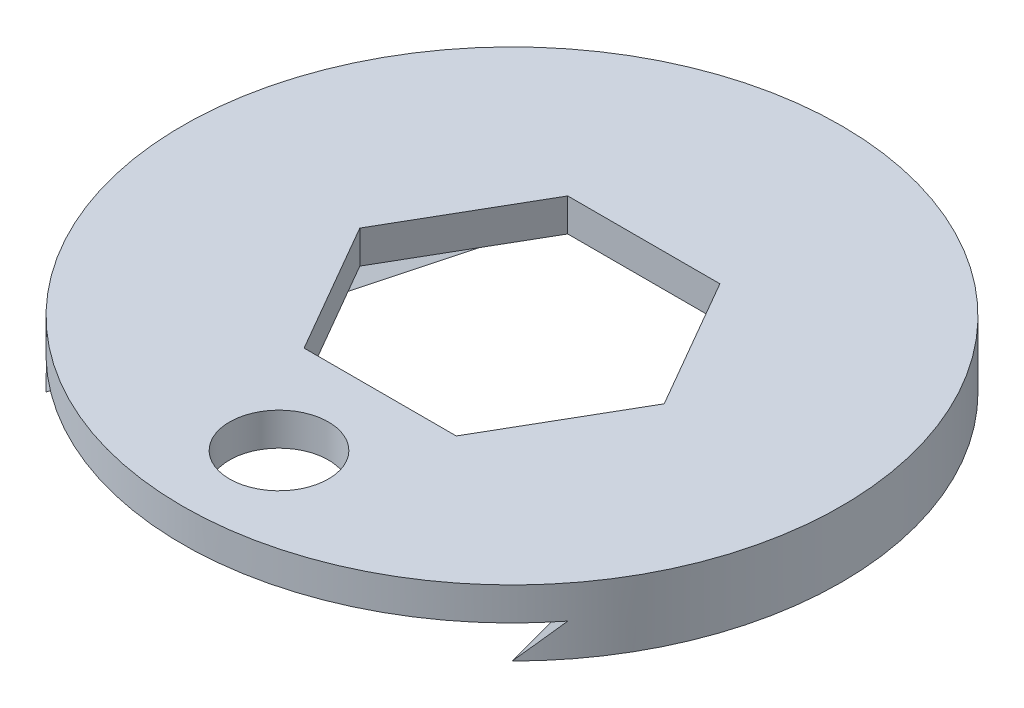
SolidWorks part; units mm, degrees
ref_plane "Front Plane" through (0, 0, 0) normal (0, 0, 1) x (1, 0, 0)
ref_plane "Top Plane" through (0, 0, 0) normal (0, 1, 0) x (1, 0, 0)
ref_plane "Right Plane" through (0, 0, 0) normal (1, 0, 0) x (0, 0, -1)
sketch "Sketch1" plane through (0, 0, 0) normal (0, 1, 0) x (1, 0, 0)
  line L0 (-35.3553, -35.3553) -> (-12.941, 48.2963)
  line L1 (-35.3553, -35.3553) -> (35.3553, -35.3553) construction
  line L2 (-35.3553, -35.3553) -> (-35.3553, 35.3553) construction
  line L3 (-35.3553, 35.3553) -> (35.3553, 35.3553) construction
  line L4 (35.3553, -35.3553) -> (35.3553, 35.3553) construction
  line L5 (-35.3553, -35.3553) -> (35.3553, 35.3553) construction
  line L6 (-35.3553, 35.3553) -> (35.3553, -35.3553) construction
  line L7 (0, 96.5926) -> (0, -94.4212) construction
  line L8 (35.3553, -35.3553) -> (12.941, 48.2963)
  circle A0 centre (0, 0) radius 50
  circle A1 centre (0, -35.3553) radius 7.5
  dimension "D1" = 100
  dimension "D3" = 15
  dimension "D2" = 15
extrude "Boss-Extrude1" add sketch "Sketch1" along normal blind 5 contours A0
extrude "Boss-Extrude2" add sketch "Sketch1<5>" against normal blind 5 contours L8 A0 | L0 A0 region at (-34.0499, 0, -9.1236) region at (34.0499, 0, -9.1236)
sketch "Sketch1<5>" plane through (0, 0, 0) normal (0, 1, 0) x (1, 0, 0) same geometry as "Sketch1"
draft "Draft1" type of draft neutral plane draft angle 45 faces to draft 2 face at (24.1481, -2.5, -6.4705) face at (-24.1481, -2.5, -6.4705) neutral plane through (0, -5, 0) neutral plane normal (0, -1, 0) reverse direction yes parameters "D1"=45
extrude "Cut-Extrude2" cut sketch "Sketch1<8>" against normal through all both and the other way through all contours A1 region at (0, 0, 35.3553)
sketch "Sketch1<8>" plane through (0, 0, 0) normal (0, 1, 0) x (1, 0, 0) same geometry as "Sketch1"
sketch "Sketch2" plane through (0, 0, 0) normal (0, -1, 0) x (1, 0, 0)
  line L1 (23.094, 0) -> (11.547, 20)
  line L2 (11.547, 20) -> (-11.547, 20)
  line L3 (-11.547, 20) -> (-23.094, 0)
  line L4 (-23.094, 0) -> (-11.547, -20)
  line L5 (-11.547, -20) -> (11.547, -20)
  line L6 (11.547, -20) -> (23.094, 0)
  circle A0 centre (0, 0) radius 20 construction
extrude "Cut-Extrude3" cut sketch "Sketch2" against normal through all
